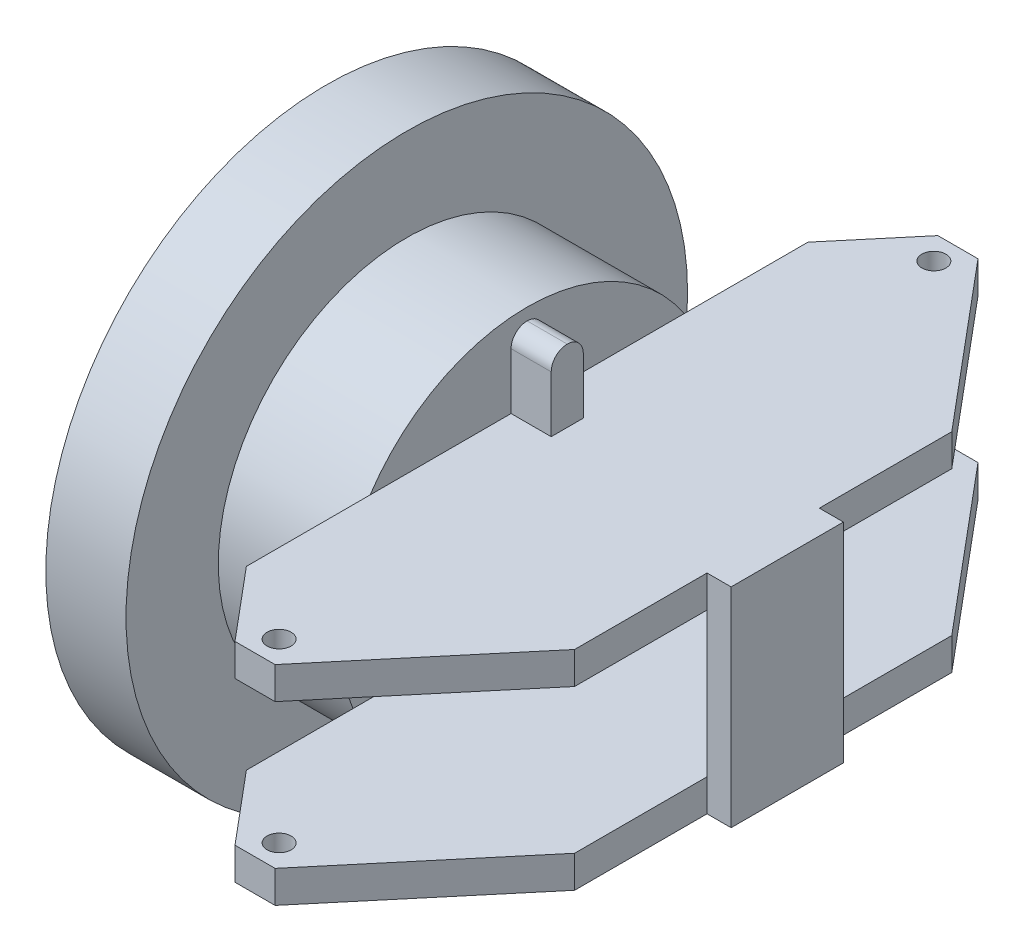
SolidWorks part; units mm, degrees
ref_plane "Front Plane" through (0, 0, 0) normal (0, 0, 1) x (1, 0, 0)
ref_plane "Top Plane" through (0, 0, 0) normal (0, 1, 0) x (1, 0, 0)
ref_plane "Right Plane" through (0, 0, 0) normal (1, 0, 0) x (0, 0, -1)
sketch "Sketch1" plane through (0, 0, 0) normal (1, 0, 0) x (0, 0, -1)
  circle A0 centre (0, 0) radius 35
  dimension "D1" = 70
extrude "Boss-Extrude2" add sketch "Sketch1" along normal blind 10
sketch "Sketch3" plane through (10, 0, 0) normal (1, 0, 0) x (0, 0, -1)
  circle A0 centre (0, 0) radius 23.5
  dimension "D1" = 47
extrude "Boss-Extrude3" add sketch "Sketch3" along normal blind 15
ref_plane "Plane1" through (0, 13, 0) normal (0, 1, 0) x (1, 0, 0)
sketch "Sketch5" plane through (0, 13, 0) normal (0, 1, 0) x (1, 0, 0)
  line L0 (25, 35) -> (25, -35)
  line L1 (25, -23.5) -> (25, 23.5) construction
  line L2 (25, -35) -> (32.3921, -43.8095)
  line L3 (32.3921, -43.8095) -> (37.3921, -43.8095)
  line L4 (25, -35) -> (25, -59.6683) construction
  line L5 (37.3921, -43.8095) -> (54.4259, -23.5093)
  line L6 (25, -23.4147) -> (80.3952, -23.4147) construction
  line L7 (37.3921, -43.8095) -> (59.6257, -43.8095) construction
  line L8 (54.4259, -23.5093) -> (54.4259, 23.5093)
  line L9 (25, 0) -> (57.8694, 0) construction
  line L10 (37.3921, 43.8095) -> (54.4259, 23.5093)
  line L11 (32.3921, 43.8095) -> (37.3921, 43.8095)
  line L12 (25, 35) -> (32.3921, 43.8095)
  point P14 (54.4259, 0)
  dimension "D1" = 35
  dimension "D2" = 11.5
  dimension "D3" = 40
  dimension "D4" = 5
  dimension "D5" = 26.5
  dimension "D6" = 50
extrude "Boss-Extrude4" add sketch "Sketch5" against normal blind 4
sketch "Sketch7" plane through (0, 13, 0) normal (0, 1, 0) x (1, 0, 0)
  line L0 (32.3921, -43.8095) -> (37.3921, -43.8095) construction
  line L1 (34.8921, -40.8095) -> (34.8921, -43.8095) construction
  circle A0 centre (34.8921, -40.8095) radius 1.5
  dimension "D1" = 3
  dimension "D2" = 3
extrude "Cut-Extrude1" cut sketch "Sketch7" against normal blind 4
mirror "Mirror1" about plane through (0, 0, 0) normal (0, 0, 1) of "Cut-Extrude1"
mirror "Mirror2" about plane through (0, 0, 0) normal (0, 1, 0) of "Boss-Extrude4", "Mirror1"
sketch "Sketch9" plane through (25, 0, 0) normal (1, 0, 0) x (0, 0, -1)
  line L0 (0, 13) -> (0, 23.5) construction
  line L1 (19.5768, 13) -> (-19.5768, 13) construction
  line L2 (-2, 13) -> (-2, 22)
  line L3 (-2, 22) -> (2, 22)
  line L4 (2, 22) -> (2, 13)
  line L6 (-19.5768, 13) -> (19.5768, 13)
  line L7 (-2, 13) -> (2, 13)
  arc A0 (19.5768, 13) -> (-19.5768, 13) centre (0, 0) ccw construction
  arc A2 (19.5768, 13) -> (-19.5768, 13) centre (0, 0) ccw
  dimension "D1" = 9
  dimension "D2" = 2
  dimension "D3" = 2
  dimension "D4" = 0
extrude "Boss-Extrude5" add sketch "Sketch9" along normal blind 5
fillet "Fillet1" radius 2 2 edges at (27.5, 22, -2) (27.5, 22, 2)
mirror "Mirror3" about plane through (0, 0, 0) normal (0, 1, 0) of "Fillet1", "Boss-Extrude5"
sketch "Sketch10" plane through (54.4259, 0, 0) normal (1, 0, 0) x (0, 0, -1)
  line L1 (-7, -13) -> (7, -13)
  line L2 (-7, -13) -> (-7, 13)
  line L3 (-7, 13) -> (7, 13)
  line L4 (7, -13) -> (7, 13)
  line L5 (-7, -13) -> (7, 13) construction
  line L6 (-7, 13) -> (7, -13) construction
  point P0 (0, 0)
  dimension "D1" = 14
  dimension "D2" = 26
extrude "Boss-Extrude6" add sketch "Sketch10" along normal blind 3
sketch "Sketch11" plane through (0, 0, 0) normal (-1, 0, 0) x (0, 0, 1)
  circle A0 centre (0, 0) radius 10
  dimension "D1" = 20
extrude "Cut-Extrude2" cut sketch "Sketch11" against normal blind 10
